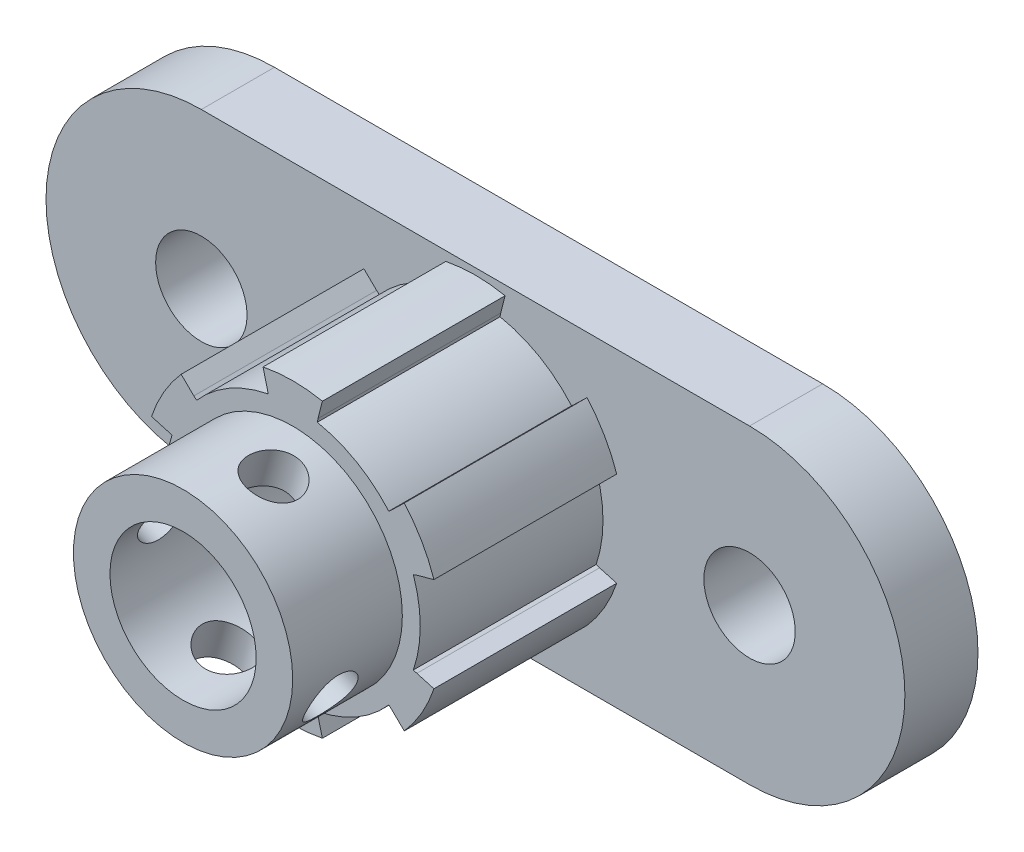
SolidWorks part; units mm, degrees
ref_plane "Front Plane" through (0, 0, 0) normal (0, 0, 1) x (1, 0, 0)
ref_plane "Top Plane" through (0, 0, 0) normal (0, 1, 0) x (1, 0, 0)
ref_plane "Right Plane" through (0, 0, 0) normal (1, 0, 0) x (0, 0, -1)
sketch "Sketch1" plane through (0, 0, 0) normal (0, 0, 1) x (1, 0, 0)
  point P0 (-7.2606, -2.1772)
  point P1 (-7.58, 0)
  line B0 (1.8734, 7.3448) -> (2.1131, 8.2848)
  line B1 (-2.1131, 8.2848) -> (-1.8734, 7.3448)
  line B2 (-5.4241, 5.2948) -> (-6.1182, 5.9724)
  line B3 (-8.2314, 2.3123) -> (-7.2975, 2.05)
  line B4 (-7.2975, -2.05) -> (-8.2314, -2.3123)
  line B5 (-6.1182, -5.9724) -> (-5.4241, -5.2948)
  line B6 (-1.8734, -7.3448) -> (-2.1131, -8.2848)
  line B7 (2.1131, -8.2848) -> (1.8734, -7.3448)
  line B8 (5.4241, -5.2948) -> (6.1182, -5.9724)
  line B9 (8.2314, -2.3123) -> (7.2975, -2.05)
  line B10 (7.2975, 2.05) -> (8.2314, 2.3123)
  line B11 (6.1182, 5.9724) -> (5.4241, 5.2948)
  arc B12 (5.4241, 5.2948) -> (1.8734, 7.3448) centre (0, 0) ccw
  arc B13 (2.1131, 8.2848) -> (-2.1131, 8.2848) centre (0, 0) ccw
  arc B14 (-1.8734, 7.3448) -> (-5.4241, 5.2948) centre (0, 0) ccw
  arc B15 (-6.1182, 5.9724) -> (-8.2314, 2.3123) centre (0, 0) ccw
  arc B16 (-7.2975, 2.05) -> (-7.2975, -2.05) centre (0, 0) ccw
  arc B17 (-8.2314, -2.3123) -> (-6.1182, -5.9724) centre (0, 0) ccw
  arc B18 (-5.4241, -5.2948) -> (-1.8734, -7.3448) centre (0, 0) ccw
  arc B19 (-2.1131, -8.2848) -> (2.1131, -8.2848) centre (0, 0) ccw
  arc B20 (1.8734, -7.3448) -> (5.4241, -5.2948) centre (0, 0) ccw
  arc B21 (6.1182, -5.9724) -> (8.2314, -2.3123) centre (0, 0) ccw
  arc B22 (7.2975, -2.05) -> (7.2975, 2.05) centre (0, 0) ccw
  arc B23 (8.2314, 2.3123) -> (6.1182, 5.9724) centre (0, 0) ccw
  circle B24 centre (-15, 0) radius 2.5
  circle B25 centre (15, 0) radius 2.5
  dimension "D1" = 15
sketch_block_instance "Block2-1"
sketch_block "Block2"
sketch_block_instance "Block3-1"
sketch_block "Block3"
sketch "Sketch3" plane through (0, 0, 0) normal (0, 0, 1) x (1, 0, 0)
  line L24 (-7.7287, 2.5866) -> (-6.7935, 2.3239)
  line L25 (-5.4093, 4.7214) -> (-6.1044, 5.3999)
  line L26 (-6.7935, -2.3239) -> (-7.7287, -2.5866)
  line L27 (-1.3842, -7.0453) -> (-1.6243, -7.9865)
  line L28 (-6.1044, -5.3999) -> (-5.4093, -4.7214)
  line L29 (1.6243, -7.9865) -> (1.3842, -7.0453)
  line L30 (5.4093, -4.7214) -> (6.1044, -5.3999)
  line L31 (7.7287, -2.5866) -> (6.7935, -2.3239)
  line L32 (6.7935, 2.3239) -> (7.7287, 2.5866)
  line L33 (6.1044, 5.3999) -> (5.4093, 4.7214)
  line L34 (1.3842, 7.0453) -> (1.6243, 7.9865)
  line L35 (-1.6243, 7.9865) -> (-1.3842, 7.0453)
  line L36 (-7.7287, 2.5866) -> (-6.7935, 2.3239)
  line L37 (-5.4093, 4.7214) -> (-6.1044, 5.3999)
  line L38 (-6.7935, -2.3239) -> (-7.7287, -2.5866)
  line L39 (-1.3842, -7.0453) -> (-1.6243, -7.9865)
  line L40 (-6.1044, -5.3999) -> (-5.4093, -4.7214)
  line L41 (1.6243, -7.9865) -> (1.3842, -7.0453)
  line L42 (5.4093, -4.7214) -> (6.1044, -5.3999)
  line L43 (7.7287, -2.5866) -> (6.7935, -2.3239)
  line L44 (6.7935, 2.3239) -> (7.7287, 2.5866)
  line L45 (6.1044, 5.3999) -> (5.4093, 4.7214)
  line L46 (1.3842, 7.0453) -> (1.6243, 7.9865)
  line L47 (-1.6243, 7.9865) -> (-1.3842, 7.0453)
  arc A25 (-6.1044, 5.3999) -> (-7.7287, 2.5866) centre (0, 0) ccw
  arc A26 (-6.7935, 2.3239) -> (-6.7935, -2.3239) centre (0, 0) ccw
  arc A27 (-7.7287, -2.5866) -> (-6.1044, -5.3999) centre (0, 0) ccw
  arc A28 (-5.4093, -4.7214) -> (-1.3842, -7.0453) centre (0, 0) ccw
  arc A29 (-1.6243, -7.9865) -> (1.6243, -7.9865) centre (0, 0) ccw
  arc A30 (1.3842, -7.0453) -> (5.4093, -4.7214) centre (0, 0) ccw
  arc A31 (6.1044, -5.3999) -> (7.7287, -2.5866) centre (0, 0) ccw
  arc A32 (6.7935, -2.3239) -> (6.7935, 2.3239) centre (0, 0) ccw
  arc A33 (7.7287, 2.5866) -> (6.1044, 5.3999) centre (0, 0) ccw
  arc A34 (5.4093, 4.7214) -> (1.3842, 7.0453) centre (0, 0) ccw
  arc A35 (1.6243, 7.9865) -> (-1.6243, 7.9865) centre (0, 0) ccw
  arc A36 (-1.3842, 7.0453) -> (-5.4093, 4.7214) centre (0, 0) ccw
  arc A37 (-6.1044, 5.3999) -> (-7.7287, 2.5866) centre (0, 0) ccw
  arc A38 (-6.7935, 2.3239) -> (-6.7935, -2.3239) centre (0, 0) ccw
  arc A39 (-7.7287, -2.5866) -> (-6.1044, -5.3999) centre (0, 0) ccw
  arc A40 (-5.4093, -4.7214) -> (-1.3842, -7.0453) centre (0, 0) ccw
  arc A41 (-1.6243, -7.9865) -> (1.6243, -7.9865) centre (0, 0) ccw
  arc A42 (1.3842, -7.0453) -> (5.4093, -4.7214) centre (0, 0) ccw
  arc A43 (6.1044, -5.3999) -> (7.7287, -2.5866) centre (0, 0) ccw
  arc A44 (6.7935, -2.3239) -> (6.7935, 2.3239) centre (0, 0) ccw
  arc A45 (7.7287, 2.5866) -> (6.1044, 5.3999) centre (0, 0) ccw
  arc A46 (5.4093, 4.7214) -> (1.3842, 7.0453) centre (0, 0) ccw
  arc A47 (1.6243, 7.9865) -> (-1.6243, 7.9865) centre (0, 0) ccw
  arc A48 (-1.3842, 7.0453) -> (-5.4093, 4.7214) centre (0, 0) ccw
  dimension "D1" = 0.4
extrude "Boss-Extrude1" add sketch "Sketch3" along normal blind 10
sketch "Sketch4" plane through (0, 0, 0) normal (0, 0, -1) x (-1, 0, 0)
  line L0 (-15, 0) -> (15, 0) construction
  line L1 (-15, 8.5) -> (15, 8.5)
  line L2 (-15, -8.5) -> (15, -8.5)
  arc A0 (-15, 8.5) -> (-15, -8.5) centre (-15, 0) ccw
  arc A1 (15, -8.5) -> (15, 8.5) centre (15, 0) ccw
  circle A2 centre (15, 0) radius 2.5 construction
  circle A3 centre (-15, 0) radius 2.5 construction
  circle A4 centre (15, 0) radius 2.5
  circle A5 centre (-15, 0) radius 2.5
  point P4 (0, 0)
  dimension "D1" = 17
extrude "Boss-Extrude2" add sketch "Sketch4" along normal blind 4
sketch "Sketch5" plane through (0, 0, -4) normal (0, 0, -1) x (-1, 0, 0)
  circle A0 centre (0, 0) radius 4
  dimension "D1" = 8
extrude "Cut-Extrude1" cut sketch "Sketch5" against normal through all
sketch "Sketch6" plane through (0, 0, 10) normal (0, 0, 1) x (1, 0, 0)
  circle A0 centre (0, 0) radius 4 construction
  circle A1 centre (0, 0) radius 4
  circle A2 centre (0, 0) radius 6
  dimension "D1" = 2
extrude "Boss-Extrude3" add sketch "Sketch6" along normal blind 6
hole_wizard "Ø1.0mm Dowel Hole1" positions "3DSketch1" profile "Sketch7" hole size "Ø1.0" standard "ANSI Metric"
sketch3d "3DSketch1"
  point P0 (-1.574, -5.7899, 12.6051)
  point P2 (5.4512, -2.5069, 13.3704)
sketch "Sketch7" plane through (-1.574, -5.7899, 12.6051) normal (0, 0, 1) x (0.965, -0.2623, 0)
  line L0 (0, 0) -> (0, 34)
  line L1 (0, 34) -> (1.4, 33.1588)
  line L2 (1.4, 33.1588) -> (1.4, 0)
  line L5 (1.4, 0) -> (0, 0)
  line L10 (0, 34) -> (-1.4, 33.1588) construction
  line L11 (0, -6.35) -> (0, 107.95) construction
  dimension "Hole Dia." = 2.8
  dimension "Hole Depth" = 34
  dimension "Drill Angle" = 118
sketch "Sketch8" plane through (0, 0, 10) normal (0, 0, 1) x (1, 0, 0)
  line L0 (-5.4093, 4.7214) -> (-5.2586, 4.5899)
  line L1 (-1.3842, 7.0453) -> (-1.3456, 6.8491)
  line L2 (5.4093, 4.7214) -> (5.2586, 4.5899)
  line L3 (1.3842, 7.0453) -> (1.3456, 6.8491)
  line L4 (6.7935, -2.3239) -> (6.6043, -2.2592)
  line L5 (6.7935, 2.3239) -> (6.6043, 2.2592)
  line L6 (1.3842, -7.0453) -> (1.3456, -6.8491)
  line L7 (5.4093, -4.7214) -> (5.2586, -4.5899)
  line L8 (-5.4093, -4.7214) -> (-5.2586, -4.5899)
  line L9 (-1.3842, -7.0453) -> (-1.3456, -6.8491)
  line L10 (-6.7935, 2.3239) -> (-6.6043, 2.2592)
  line L11 (-6.7935, -2.3239) -> (-6.6043, -2.2592)
  arc A0 (-1.3842, 7.0453) -> (-5.4093, 4.7214) centre (0, 0) ccw construction
  arc A1 (-1.3842, 7.0453) -> (-5.4093, 4.7214) centre (0, 0) ccw
  arc A2 (-1.3456, 6.8491) -> (-5.2586, 4.5899) centre (0, 0) ccw
  arc A3 (5.4093, 4.7214) -> (1.3842, 7.0453) centre (0, 0) ccw
  arc A4 (5.2586, 4.5899) -> (1.3456, 6.8491) centre (0, 0) ccw
  arc A5 (6.7935, -2.3239) -> (6.7935, 2.3239) centre (0, 0) ccw
  arc A6 (6.6043, -2.2592) -> (6.6043, 2.2592) centre (0, 0) ccw
  arc A7 (1.3842, -7.0453) -> (5.4093, -4.7214) centre (0, 0) ccw
  arc A8 (1.3456, -6.8491) -> (5.2586, -4.5899) centre (0, 0) ccw
  arc A9 (-5.4093, -4.7214) -> (-1.3842, -7.0453) centre (0, 0) ccw
  arc A10 (-5.2586, -4.5899) -> (-1.3456, -6.8491) centre (0, 0) ccw
  arc A11 (-6.7935, 2.3239) -> (-6.7935, -2.3239) centre (0, 0) ccw
  arc A12 (-6.6043, 2.2592) -> (-6.6043, -2.2592) centre (0, 0) ccw
  point P28 (0, 0)
  dimension "D1" = 0.2
  dimension "D2" = 6
extrude "Cut-Extrude2" cut sketch "Sketch8" against normal blind 10
